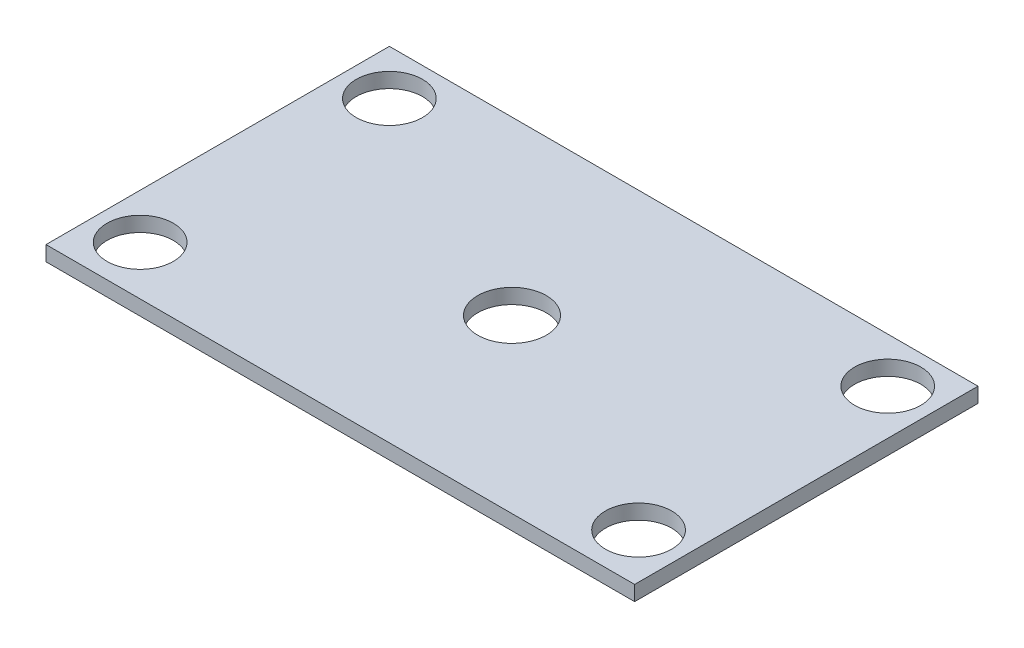
SolidWorks part; units mm, degrees
ref_plane "Front Plane" through (0, 0, 0) normal (0, 0, 1) x (1, 0, 0)
ref_plane "Top Plane" through (0, 0, 0) normal (0, 1, 0) x (1, 0, 0)
ref_plane "Right Plane" through (0, 0, 0) normal (1, 0, 0) x (0, 0, -1)
sketch "Sketch1" plane through (0, 0, 0) normal (0, 1, 0) x (1, 0, 0)
  line L0 (4.6, 30.4) -> (0, 30.4) construction
  line L1 (0, 0) -> (60, 0)
  line L2 (0, 0) -> (0, 35)
  line L3 (0, 35) -> (60, 35)
  line L4 (60, 0) -> (60, 35)
  line L5 (4.6, 30.4) -> (55.4, 30.4) construction
  line L6 (4.6, 30.4) -> (4.6, 5) construction
  line L7 (4.6, 5) -> (55.4, 5) construction
  line L8 (55.4, 30.4) -> (55.4, 5) construction
  line L9 (4.6, 30.4) -> (4.6, 35) construction
  circle A0 centre (4.6, 30.4) radius 3.3782
  circle A1 centre (55.4, 30.4) radius 3.3782
  circle A2 centre (4.6, 5) radius 3.3782
  circle A3 centre (55.4, 5) radius 3.3782
  circle A4 centre (30, 17.5) radius 3.5
  point P13 (30, 30.4)
  point P14 (30, 35)
  point P20 (60, 17.5)
  dimension "D5" = 6.7564
  dimension "D6" = 7
  dimension "D1" = 60
  dimension "D2" = 35
  dimension "D3" = 50.8
  dimension "D4" = 25.4
extrude "Boss-Extrude1" add sketch "Sketch1" along normal blind 1.524
